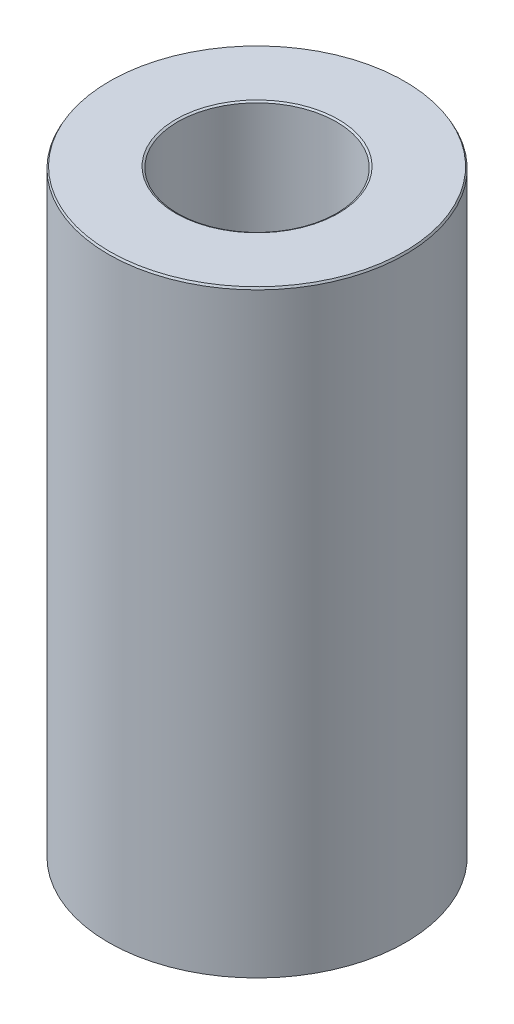
SolidWorks part; units mm, degrees
ref_plane "Front Plane" through (0, 0, 0) normal (0, 0, 1) x (1, 0, 0)
ref_plane "Top Plane" through (0, 0, 0) normal (0, 1, 0) x (1, 0, 0)
ref_plane "Right Plane" through (0, 0, 0) normal (1, 0, 0) x (0, 0, -1)
sketch "Sketch1" plane through (0, 0, 0) normal (0, 1, 0) x (1, 0, 0)
  circle A0 centre (0, 0) radius 25
  dimension "SLEEVE_OD" = 50
extrude "Boss-Extrude1" add sketch "Sketch1" along normal blind 100.7711
sketch "Sketch2" plane through (0, 0, 0) normal (0, 1, 0) x (1, 0, 0)
  circle A0 centre (0, 0) radius 13.3612
  dimension "BORE_D" = 26.7225
extrude "Cut-Extrude1" cut sketch "Sketch2" along normal through all
chamfer "Chamfer1" distance 0.3262 angle 30 4 edges at (0, 100.7711, 13.3612) (0, 0, 13.3612) (0, 0, 25) (0, 100.7711, 25) first distance on face at (0, 100.7711, 13.3612) first distance on face at (0, 0, 13.3612) first distance on face at (0, 100.7711, 25)
